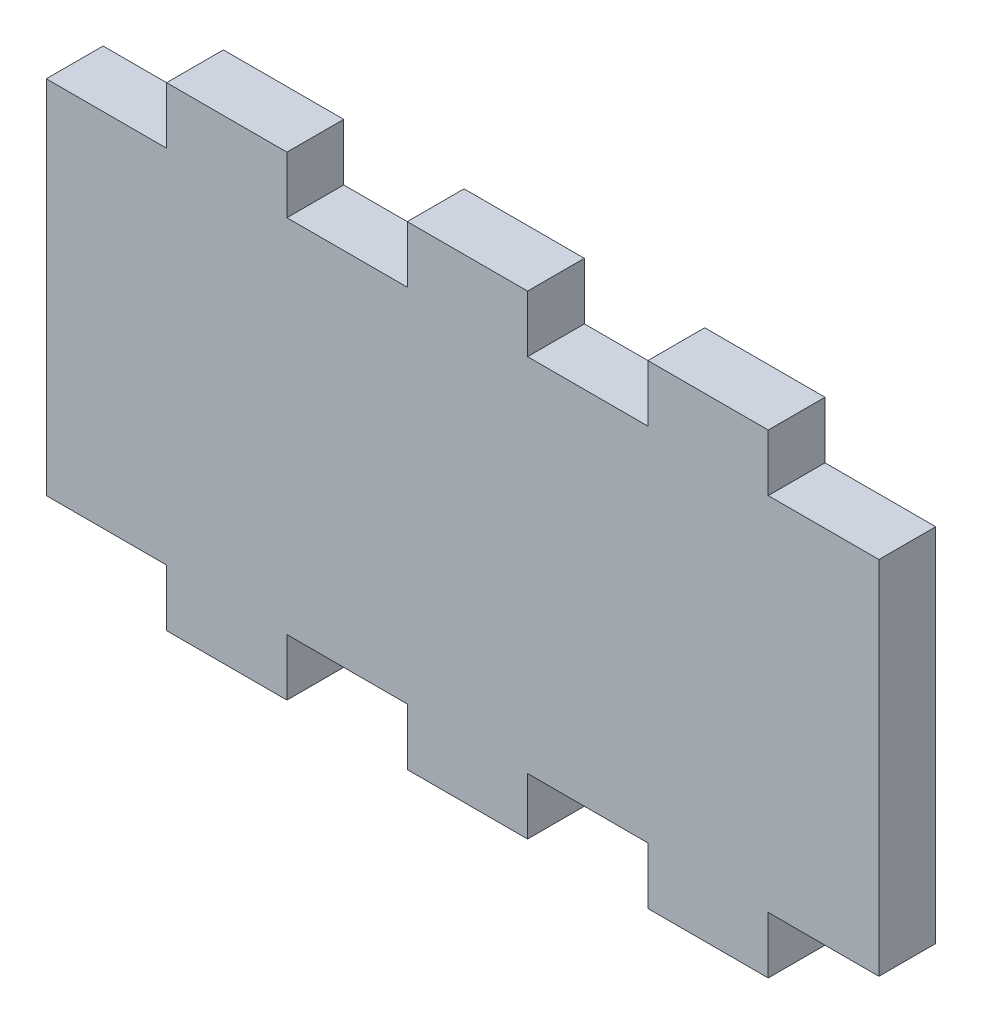
SolidWorks part; units mm, degrees
ref_plane "Front Plane" through (0, 0, 0) normal (0, 0, 1) x (1, 0, 0)
ref_plane "Top Plane" through (0, 0, 0) normal (0, 1, 0) x (1, 0, 0)
ref_plane "Right Plane" through (0, 0, 0) normal (1, 0, 0) x (0, 0, -1)
sketch "Sketch1" plane through (0, 0, 0) normal (0, 0, 1) x (1, 0, 0)
  line L1 (-21.971, -9.525) -> (21.971, -9.525)
  line L2 (-21.971, -9.525) -> (-21.971, 9.525)
  line L3 (-21.971, 9.525) -> (21.971, 9.525)
  line L4 (21.971, -9.525) -> (21.971, 9.525)
  line L5 (-21.971, -9.525) -> (21.971, 9.525) construction
  line L6 (-21.971, 9.525) -> (21.971, -9.525) construction
  point P0 (0, 0)
  dimension "D1" = 19.05
  dimension "D2" = 43.942
extrude "Body" add sketch "Sketch1" along normal blind 2.9972
sketch "Sketch2" plane through (0, 9.525, 0) normal (0, 1, 0) x (1, 0, 0)
  line L0 (21.971, 0) -> (-21.971, 0) construction
  line L1 (-15.621, 0) -> (-9.271, 0)
  line L2 (-15.621, 0) -> (-15.621, -2.9972)
  line L3 (-15.621, -2.9972) -> (-9.271, -2.9972)
  line L4 (-9.271, 0) -> (-9.271, -2.9972)
  line L5 (21.971, -2.9972) -> (-21.971, -2.9972) construction
  line L6 (-21.971, -2.9972) -> (-21.971, 0) construction
  dimension "D1" = 6.35
  dimension "D2" = 6.35
extrude "Tab" add sketch "Sketch2" along normal blind 2.9972
sketch "Sketch3" plane through (0, 0, 2.9972) normal (0, 0, 1) x (1, 0, 0)
  line L0 (-14.859, 12.5222) -> (-14.859, 8.255)
  line L1 (-15.621, 12.5222) -> (-9.271, 12.5222) construction
  line L2 (-14.859, 8.255) -> (-14.224, 8.255)
  line L3 (-14.224, 8.255) -> (-14.224, 12.5222)
  line L4 (-15.621, 9.525) -> (-9.271, 9.525) construction
  line L5 (-12.446, 9.525) -> (-12.446, 12.5222) construction
  line L6 (-14.859, 12.5222) -> (-14.224, 12.5222)
  line L7 (-10.033, 12.5222) -> (-10.668, 12.5222)
  line L8 (-10.668, 8.255) -> (-10.668, 12.5222)
  line L9 (-10.033, 8.255) -> (-10.668, 8.255)
  line L10 (-10.033, 12.5222) -> (-10.033, 8.255)
  line L11 (-8.636, 9.525) -> (-8.636, 8.255)
  line L12 (-15.621, 9.525) -> (-16.256, 9.525)
  line L13 (-15.621, 9.525) -> (-15.621, 8.255)
  line L14 (-15.621, 8.255) -> (-16.256, 8.255)
  line L15 (-16.256, 9.525) -> (-16.256, 8.255)
  line L16 (-9.271, 8.255) -> (-8.636, 8.255)
  line L17 (-9.271, 9.525) -> (-9.271, 8.255)
  line L18 (-9.271, 9.525) -> (-8.636, 9.525)
  line L19 (-15.621, 12.5222) -> (-15.621, 9.525) construction
  dimension "D1" = 0.635
  dimension "D2" = 0.635
  dimension "D3" = 1.27
  dimension "D4" = 0.762
extrude "Slots" [suppressed] cut sketch "Sketch3" against normal through all
fillet "Fillet1" [suppressed] radius 0.254
ref_plane "Tab Midplane" [suppressed] through (-12.7, 0, 0) normal (-1, 0, 0) x (0, 0, 1)
ref_plane "Body Horizontal Midplane" through (0, 0, 0) normal (0, 1, 0) x (1, 0, 0)
ref_plane "Body Vertical Midplane" through (0, 0, 0) normal (-1, 0, 0) x (0, 0, 1)
pattern_linear "LPattern1" count 3 spacing 12.7 along (1, 0, 0) of "Tab"
mirror "Mirror1" about plane through (0, 0, 0) normal (0, 1, 0) of "LPattern1"
